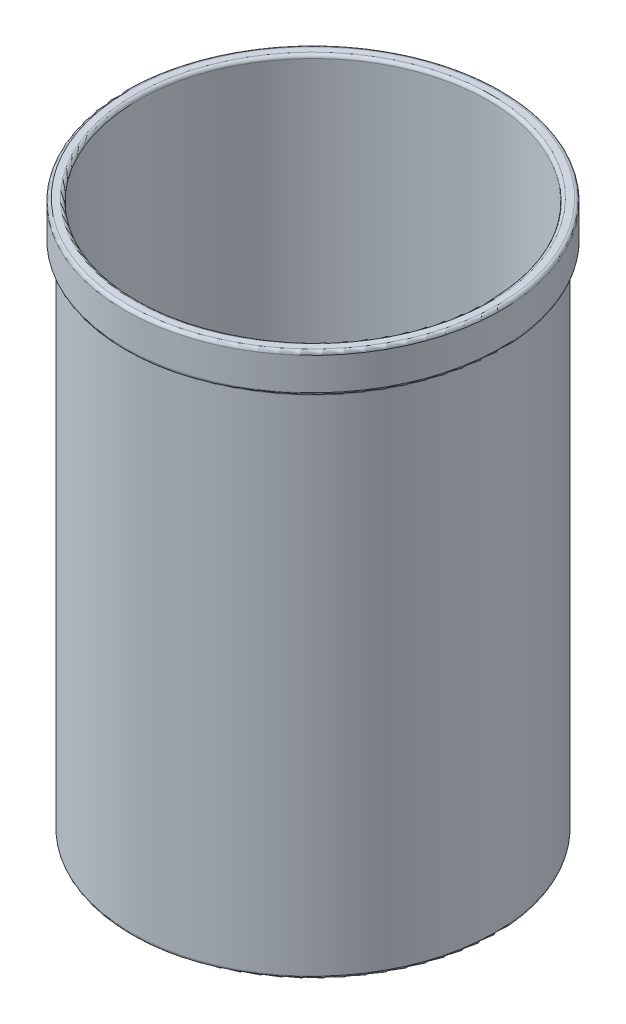
SolidWorks part; units mm, degrees
material "Cast iron, nodular graphite, EN GJS 450 10"
ref_plane "Front Plane" through (0, 0, 0) normal (0, 0, 1) x (1, 0, 0)
ref_plane "Top Plane" through (0, 0, 0) normal (0, 1, 0) x (1, 0, 0)
ref_plane "Right Plane" through (0, 0, 0) normal (1, 0, 0) x (0, 0, -1)
sketch "Sketch1" plane through (0, 0, 0) normal (0, 1, 0) x (1, 0, 0)
  circle A0 centre (0, 0) radius 56.1
  circle A1 centre (0, 0) radius 54.1
  dimension "D1" = 54.1
  dimension "D2" = 2
extrude "Boss-Extrude1" add sketch "Sketch1" along normal blind 169.33
sketch "Sketch3" plane through (0, 169.33, 0) normal (0, 1, 0) x (1, 0, 0)
  circle A0 centre (0, 0) radius 56.1 construction
  circle A1 centre (0, 0) radius 56.1
  circle A2 centre (0, 0) radius 58.1
  dimension "D1" = 2
extrude "Boss-Extrude2" add sketch "Sketch3" against normal blind 12
fillet "Fillet1" radius 1 6 edges at (0, 0, 54.1) (0, 0, 56.1) (0, 157.33, 56.1) (0, 169.33, 54.1) (0, 157.33, 58.1) (0, 169.33, 58.1)
equation "\"PS_Radius\"= 108 / 2"
equation "\"PS_Clearance\"= 0.1"
equation "\"Liner_Radius\"= \"PS_Clearance\" + \"PS_Radius\""
equation "\"D1@Sketch1\"=\"Liner_Radius\""
equation "\"Liner_Thickness\"= 2"
equation "\"D2@Sketch1\"=\"Liner_Thickness\""
equation "\"Cylinder_Length\"= 169.33"
equation "\"D1@Boss-Extrude1\"=\"Cylinder_Length\""
equation "\"Lip_Height\"= 12"
equation "\"D1@Boss-Extrude2\"=\"Lip_Height\""
